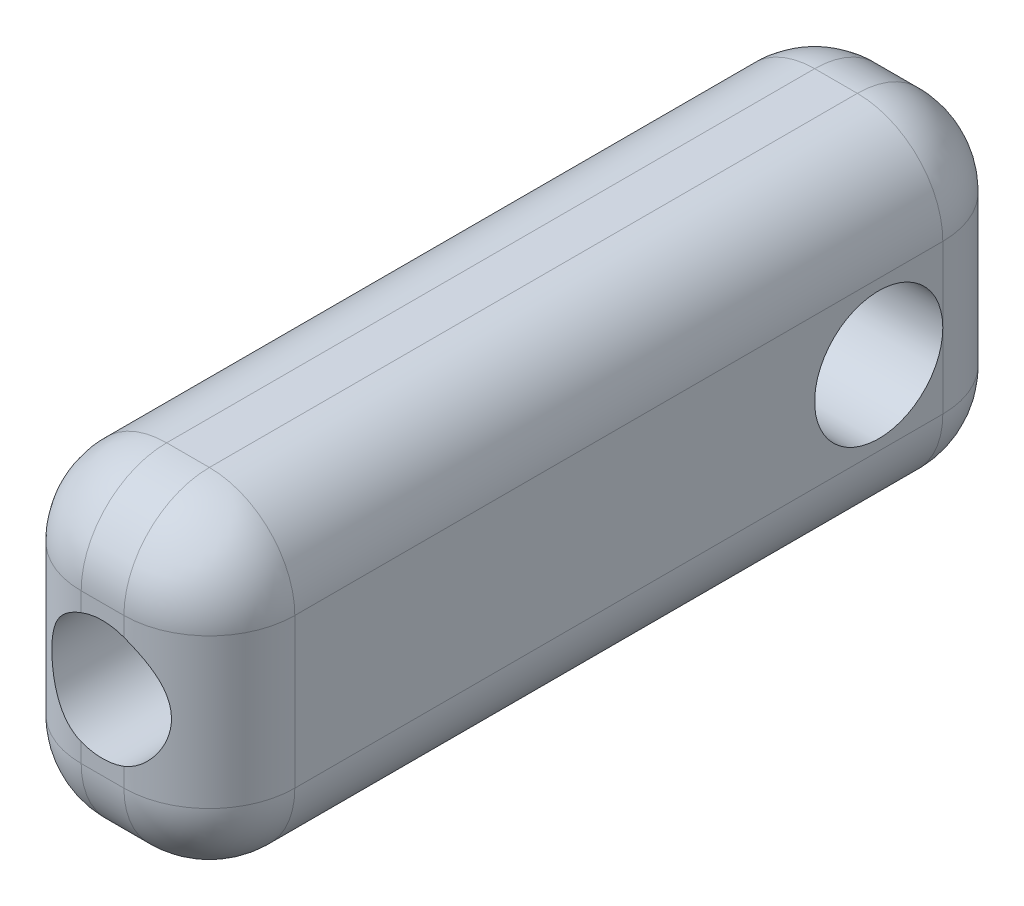
SolidWorks part; units mm, degrees
ref_plane "Front Plane" through (0, 0, 0) normal (0, 0, 1) x (1, 0, 0)
ref_plane "Top Plane" through (0, 0, 0) normal (0, 1, 0) x (1, 0, 0)
ref_plane "Right Plane" through (0, 0, 0) normal (1, 0, 0) x (0, 0, -1)
sketch "Sketch1" plane through (0, 0, 0) normal (0, 1, 0) x (1, 0, 0)
  line L0 (0, 0) -> (0, 24.3398)
  line L3 (0, 24.3398) -> (6.35, 24.3398)
  line L4 (6.35, 24.3398) -> (6.35, 0)
  line L6 (6.35, 0) -> (0, 0)
  point P1 (6.35, 0.4395)
  point P3 (0, 20.8013)
  point P4 (0, 20.3046)
  dimension "D1" = 6.35
extrude "Boss-Extrude1" add sketch "Sketch1" along normal mid plane 9.525
sketch "Sketch2" plane through (0, 0, 0) normal (0, 0, 1) x (1, 0, 0)
  line L0 (6.35, 0) -> (3.175, 0) construction
  line L2 (3.175, 0) -> (0, 0) construction
  line L3 (6.35, 4.7625) -> (6.35, -4.7625) construction
  circle A0 centre (3.175, 0) radius 1.778
  point P3 (6.35, 0)
  dimension "D1" = 3.556
extrude "Cut-Extrude1" cut sketch "Sketch2" against normal blind 9.525
sketch "Sketch3" plane through (0, 0, 0) normal (-1, 0, 0) x (0, 0, 1)
  line L0 (-19.8948, 0) -> (-19.8948, 4.7625) construction
  line L2 (-19.8948, 0) -> (-19.8948, -4.7625) construction
  line L4 (-24.3398, -4.7625) -> (0, -4.7625) construction
  line L6 (-24.3398, 4.7625) -> (0, 4.7625) construction
  line L8 (-24.3398, 4.7625) -> (-24.3398, -4.7625) construction
  circle A0 centre (-19.8948, 0) radius 1.905
  point P2 (0, 0)
  point P4 (-18.9461, 4.7625)
  point P7 (-18.9738, -4.7625)
  point P9 (0, 0)
  dimension "D1" = 3.81
  dimension "D2" = 4.445
extrude "Cut-Extrude2" cut sketch "Sketch3" against normal blind 9.525
fillet "Fillet1" radius 2.54 12 edges at (6.35, -4.7625, -12.1699) (0, -4.7625, -12.1699) (3.175, -4.7625, 0) (0, 4.7625, -12.1699) (6.35, 4.7625, -12.1699) (3.175, 4.7625, 0) (6.35, 0, -24.3398) (3.175, 4.7625, -24.3398) (0, 0, -24.3398) (3.175, -4.7625, -24.3398) (0, 0, 0) (6.35, 0, 0)
